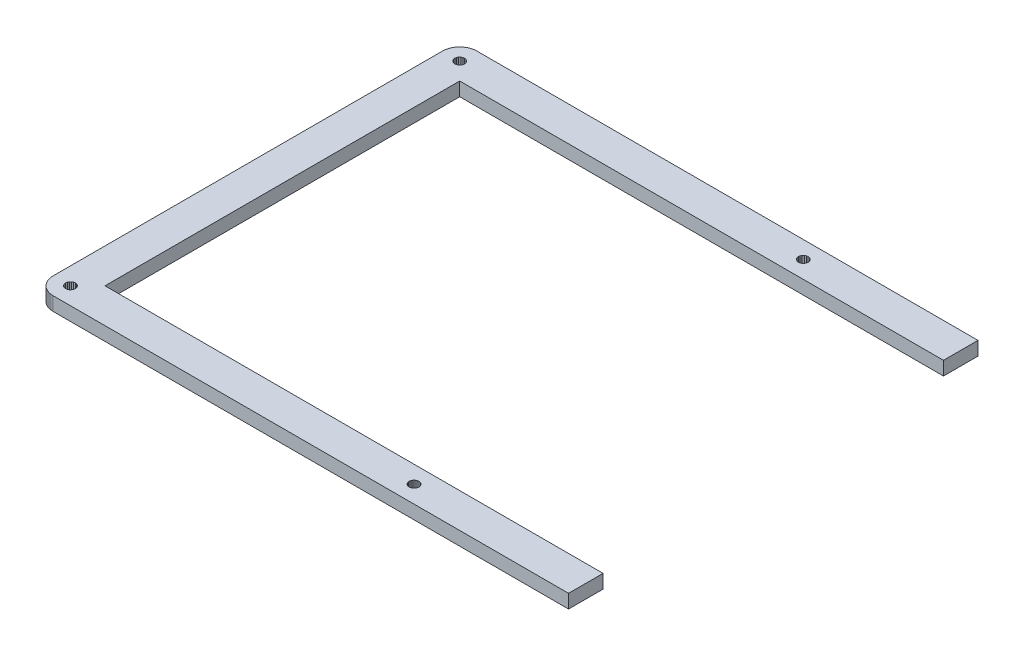
SolidWorks part; units mm, degrees
material "Copper"
ref_plane "Front Plane" through (0, 0, 0) normal (0, 0, 1) x (1, 0, 0)
ref_plane "Top Plane" through (0, 0, 0) normal (0, 1, 0) x (1, 0, 0)
ref_plane "Right Plane" through (0, 0, 0) normal (1, 0, 0) x (0, 0, -1)
sketch "Sketch1" plane through (0, 0, 0) normal (0, 1, 0) x (1, 0, 0)
  line L0 (365.806, 147.967) -> (366.279, 147.949)
  line L1 (366.279, 147.949) -> (366.748, 147.894)
  line L2 (366.748, 147.894) -> (367.21, 147.803)
  line L3 (367.21, 147.803) -> (367.661, 147.675)
  line L4 (367.661, 147.675) -> (368.106, 147.511)
  line L5 (368.106, 147.511) -> (368.533, 147.314)
  line L6 (368.533, 147.314) -> (368.942, 147.085)
  line L7 (368.942, 147.085) -> (369.334, 146.822)
  line L8 (369.334, 146.822) -> (369.704, 146.529)
  line L9 (369.704, 146.529) -> (370.05, 146.21)
  line L10 (370.05, 146.21) -> (370.371, 145.865)
  line L11 (370.371, 145.865) -> (370.664, 145.495)
  line L12 (370.664, 145.495) -> (370.925, 145.102)
  line L13 (370.925, 145.102) -> (371.154, 144.691)
  line L14 (371.154, 144.691) -> (371.352, 144.264)
  line L15 (371.352, 144.264) -> (371.514, 143.822)
  line L16 (371.514, 143.822) -> (371.641, 143.368)
  line L17 (371.641, 143.368) -> (371.733, 142.907)
  line L18 (371.733, 142.907) -> (371.789, 142.44)
  line L19 (371.789, 142.44) -> (371.807, 141.967)
  line L20 (371.807, 141.967) -> (371.807, 6.0909)
  line L21 (371.807, 6.0909) -> (371.789, 5.621)
  line L22 (371.789, 5.621) -> (371.733, 5.1539)
  line L23 (371.733, 5.1539) -> (371.641, 4.6909)
  line L24 (371.641, 4.6909) -> (371.514, 4.2375)
  line L25 (371.514, 4.2375) -> (371.352, 3.7951)
  line L26 (371.352, 3.7951) -> (371.154, 3.3679)
  line L27 (371.154, 3.3679) -> (370.925, 2.9573)
  line L28 (370.925, 2.9573) -> (370.664, 2.5645)
  line L29 (370.664, 2.5645) -> (370.371, 2.1966)
  line L30 (370.371, 2.1966) -> (370.05, 1.8493)
  line L31 (370.05, 1.8493) -> (369.704, 1.5296)
  line L32 (369.704, 1.5296) -> (369.334, 1.2375)
  line L33 (369.334, 1.2375) -> (368.942, 0.9757)
  line L34 (368.942, 0.9757) -> (368.533, 0.7455)
  line L35 (368.533, 0.7455) -> (368.106, 0.5498)
  line L36 (368.106, 0.5498) -> (367.661, 0.3859)
  line L37 (367.661, 0.3859) -> (367.21, 0.2577)
  line L38 (367.21, 0.2577) -> (366.748, 0.1654)
  line L39 (366.748, 0.1654) -> (366.279, 0.1102)
  line L40 (366.279, 0.1102) -> (365.806, 0.091)
  line L41 (365.806, 0.091) -> (6.095, 0.091)
  line L42 (6.095, 0.091) -> (5.6238, 0.1102)
  line L43 (5.6238, 0.1102) -> (5.1553, 0.1654)
  line L44 (5.1553, 0.1654) -> (4.6936, 0.2577)
  line L45 (4.6936, 0.2577) -> (4.2402, 0.3859)
  line L46 (4.2402, 0.3859) -> (3.7979, 0.5498)
  line L47 (3.7979, 0.5498) -> (3.3707, 0.7455)
  line L48 (3.3707, 0.7455) -> (2.96, 0.9757)
  line L49 (2.96, 0.9757) -> (2.5673, 1.2375)
  line L50 (2.5673, 1.2375) -> (2.198, 1.5296)
  line L51 (2.198, 1.5296) -> (1.8521, 1.8493)
  line L52 (1.8521, 1.8493) -> (1.5324, 2.1966)
  line L53 (1.5324, 2.1966) -> (1.2402, 2.5645)
  line L54 (1.2402, 2.5645) -> (0.9784, 2.9573)
  line L55 (0.9784, 2.9573) -> (0.7483, 3.3679)
  line L56 (0.7483, 3.3679) -> (0.5512, 3.7951)
  line L57 (0.5512, 3.7951) -> (0.3872, 4.2375)
  line L58 (0.3872, 4.2375) -> (0.2591, 4.6909)
  line L59 (0.2591, 4.6909) -> (0.1681, 5.1539)
  line L60 (0.1681, 5.1539) -> (0.113, 5.621)
  line L61 (0.113, 5.621) -> (0.0937, 6.0923)
  line L62 (0.0937, 6.0923) -> (0.0951, 141.967)
  line L63 (0.0951, 141.967) -> (0.113, 142.44)
  line L64 (0.113, 142.44) -> (0.1681, 142.907)
  line L65 (0.1681, 142.907) -> (0.2591, 143.368)
  line L66 (0.2591, 143.368) -> (0.3872, 143.822)
  line L67 (0.3872, 143.822) -> (0.5512, 144.264)
  line L68 (0.5512, 144.264) -> (0.7483, 144.691)
  line L69 (0.7483, 144.691) -> (0.9784, 145.102)
  line L70 (0.9784, 145.102) -> (1.2402, 145.495)
  line L71 (1.2402, 145.495) -> (1.5324, 145.865)
  line L72 (1.5324, 145.865) -> (1.8521, 146.21)
  line L73 (1.8521, 146.21) -> (2.198, 146.529)
  line L74 (2.198, 146.529) -> (2.5673, 146.822)
  line L75 (2.5673, 146.822) -> (2.96, 147.085)
  line L76 (2.96, 147.085) -> (3.3707, 147.314)
  line L77 (3.3707, 147.314) -> (3.7979, 147.511)
  line L78 (3.7979, 147.511) -> (4.2402, 147.675)
  line L79 (4.2402, 147.675) -> (4.6936, 147.803)
  line L80 (4.6936, 147.803) -> (5.1553, 147.894)
  line L81 (5.1553, 147.894) -> (5.6238, 147.949)
  line L82 (5.6238, 147.949) -> (6.095, 147.968)
  line L83 (6.095, 147.968) -> (365.806, 147.967)
  line L84 (365.252, 7.757) -> (364.769, 7.5117)
  line L85 (364.769, 7.5117) -> (364.388, 7.13)
  line L86 (364.388, 7.13) -> (364.141, 6.6504)
  line L87 (364.141, 6.6504) -> (364.06, 6.1157)
  line L88 (364.06, 6.1157) -> (364.141, 5.5838)
  line L89 (364.141, 5.5838) -> (364.388, 5.1029)
  line L90 (364.388, 5.1029) -> (364.769, 4.7211)
  line L91 (364.769, 4.7211) -> (365.252, 4.4759)
  line L92 (365.252, 4.4759) -> (365.781, 4.3918)
  line L93 (365.781, 4.3918) -> (366.317, 4.4759)
  line L94 (366.317, 4.4759) -> (366.797, 4.7211)
  line L95 (366.797, 4.7211) -> (367.178, 5.1029)
  line L96 (367.178, 5.1029) -> (367.425, 5.5838)
  line L97 (367.425, 5.5838) -> (367.506, 6.1157)
  line L98 (367.506, 6.1157) -> (367.425, 6.6504)
  line L99 (367.425, 6.6504) -> (367.178, 7.13)
  line L100 (367.178, 7.13) -> (366.797, 7.5117)
  line L101 (366.797, 7.5117) -> (366.317, 7.757)
  line L102 (366.317, 7.757) -> (365.781, 7.8411)
  line L103 (365.781, 7.8411) -> (365.252, 7.757)
  line L104 (245.361, 7.757) -> (244.88, 7.5117)
  line L105 (244.88, 7.5117) -> (244.5, 7.13)
  line L106 (244.5, 7.13) -> (244.255, 6.6504)
  line L107 (244.255, 6.6504) -> (244.169, 6.1157)
  line L108 (244.169, 6.1157) -> (244.255, 5.5838)
  line L109 (244.255, 5.5838) -> (244.5, 5.1029)
  line L110 (244.5, 5.1029) -> (244.88, 4.7211)
  line L111 (244.88, 4.7211) -> (245.361, 4.4759)
  line L112 (245.361, 4.4759) -> (245.894, 4.3918)
  line L113 (245.894, 4.3918) -> (246.428, 4.4759)
  line L114 (246.428, 4.4759) -> (246.908, 4.7211)
  line L115 (246.908, 4.7211) -> (247.29, 5.1029)
  line L116 (247.29, 5.1029) -> (247.536, 5.5838)
  line L117 (247.536, 5.5838) -> (247.62, 6.1157)
  line L118 (247.62, 6.1157) -> (247.536, 6.6504)
  line L119 (247.536, 6.6504) -> (247.29, 7.13)
  line L120 (247.29, 7.13) -> (246.908, 7.5117)
  line L121 (246.908, 7.5117) -> (246.428, 7.757)
  line L122 (246.428, 7.757) -> (245.894, 7.8411)
  line L123 (245.894, 7.8411) -> (245.361, 7.757)
  line L124 (125.473, 7.757) -> (124.992, 7.5117)
  line L125 (124.992, 7.5117) -> (124.612, 7.13)
  line L126 (124.612, 7.13) -> (124.365, 6.6504)
  line L127 (124.365, 6.6504) -> (124.281, 6.1157)
  line L128 (124.281, 6.1157) -> (124.365, 5.5838)
  line L129 (124.365, 5.5838) -> (124.612, 5.1029)
  line L130 (124.612, 5.1029) -> (124.992, 4.7211)
  line L131 (124.992, 4.7211) -> (125.473, 4.4759)
  line L132 (125.473, 4.4759) -> (126.007, 4.3918)
  line L133 (126.007, 4.3918) -> (126.54, 4.4759)
  line L134 (126.54, 4.4759) -> (127.021, 4.7211)
  line L135 (127.021, 4.7211) -> (127.403, 5.1029)
  line L136 (127.403, 5.1029) -> (127.648, 5.5838)
  line L137 (127.648, 5.5838) -> (127.732, 6.1157)
  line L138 (127.732, 6.1157) -> (127.648, 6.6504)
  line L139 (127.648, 6.6504) -> (127.403, 7.13)
  line L140 (127.403, 7.13) -> (127.021, 7.5117)
  line L141 (127.021, 7.5117) -> (126.54, 7.757)
  line L142 (126.54, 7.757) -> (126.007, 7.8411)
  line L143 (126.007, 7.8411) -> (125.473, 7.757)
  line L144 (5.5852, 7.757) -> (5.1056, 7.5117)
  line L145 (5.1056, 7.5117) -> (4.7239, 7.13)
  line L146 (4.7239, 7.13) -> (4.4786, 6.6504)
  line L147 (4.4786, 6.6504) -> (4.3932, 6.1157)
  line L148 (4.3932, 6.1157) -> (4.4786, 5.5838)
  line L149 (4.4786, 5.5838) -> (4.7239, 5.1029)
  line L150 (4.7239, 5.1029) -> (5.1056, 4.7211)
  line L151 (5.1056, 4.7211) -> (5.5852, 4.4759)
  line L152 (5.5852, 4.4759) -> (6.1185, 4.3918)
  line L153 (6.1185, 4.3918) -> (6.6532, 4.4759)
  line L154 (6.6532, 4.4759) -> (7.1327, 4.7211)
  line L155 (7.1327, 4.7211) -> (7.5145, 5.1029)
  line L156 (7.5145, 5.1029) -> (7.7597, 5.5838)
  line L157 (7.7597, 5.5838) -> (7.8438, 6.1157)
  line L158 (7.8438, 6.1157) -> (7.7597, 6.6504)
  line L159 (7.7597, 6.6504) -> (7.5145, 7.13)
  line L160 (7.5145, 7.13) -> (7.1327, 7.5117)
  line L161 (7.1327, 7.5117) -> (6.6532, 7.757)
  line L162 (6.6532, 7.757) -> (6.1185, 7.8411)
  line L163 (6.1185, 7.8411) -> (5.5852, 7.757)
  line L164 (12.1447, 135.919) -> (359.759, 135.919)
  line L165 (359.759, 135.919) -> (359.759, 12.1405)
  line L166 (359.759, 12.1405) -> (12.1447, 12.1405)
  line L167 (12.1447, 12.1405) -> (12.1447, 135.919)
  line L168 (125.473, 143.583) -> (124.992, 143.338)
  line L169 (124.992, 143.338) -> (124.612, 142.956)
  line L170 (124.612, 142.956) -> (124.365, 142.477)
  line L171 (124.365, 142.477) -> (124.281, 141.942)
  line L172 (124.281, 141.942) -> (124.365, 141.409)
  line L173 (124.365, 141.409) -> (124.612, 140.929)
  line L174 (124.612, 140.929) -> (124.992, 140.547)
  line L175 (124.992, 140.547) -> (125.473, 140.302)
  line L176 (125.473, 140.302) -> (126.007, 140.217)
  line L177 (126.007, 140.217) -> (126.54, 140.302)
  line L178 (126.54, 140.302) -> (127.021, 140.547)
  line L179 (127.021, 140.547) -> (127.403, 140.929)
  line L180 (127.403, 140.929) -> (127.648, 141.409)
  line L181 (127.648, 141.409) -> (127.732, 141.942)
  line L182 (127.732, 141.942) -> (127.648, 142.477)
  line L183 (127.648, 142.477) -> (127.403, 142.956)
  line L184 (127.403, 142.956) -> (127.021, 143.338)
  line L185 (127.021, 143.338) -> (126.54, 143.583)
  line L186 (126.54, 143.583) -> (126.007, 143.667)
  line L187 (126.007, 143.667) -> (125.473, 143.583)
  line L188 (245.361, 143.583) -> (244.88, 143.338)
  line L189 (244.88, 143.338) -> (244.5, 142.956)
  line L190 (244.5, 142.956) -> (244.255, 142.477)
  line L191 (244.255, 142.477) -> (244.169, 141.942)
  line L192 (244.169, 141.942) -> (244.255, 141.409)
  line L193 (244.255, 141.409) -> (244.5, 140.929)
  line L194 (244.5, 140.929) -> (244.88, 140.547)
  line L195 (244.88, 140.547) -> (245.361, 140.302)
  line L196 (245.361, 140.302) -> (245.894, 140.217)
  line L197 (245.894, 140.217) -> (246.428, 140.302)
  line L198 (246.428, 140.302) -> (246.908, 140.547)
  line L199 (246.908, 140.547) -> (247.29, 140.929)
  line L200 (247.29, 140.929) -> (247.536, 141.409)
  line L201 (247.536, 141.409) -> (247.62, 141.942)
  line L202 (247.62, 141.942) -> (247.536, 142.477)
  line L203 (247.536, 142.477) -> (247.29, 142.956)
  line L204 (247.29, 142.956) -> (246.908, 143.338)
  line L205 (246.908, 143.338) -> (246.428, 143.583)
  line L206 (246.428, 143.583) -> (245.894, 143.667)
  line L207 (245.894, 143.667) -> (245.361, 143.583)
  line L208 (365.252, 143.583) -> (364.769, 143.338)
  line L209 (364.769, 143.338) -> (364.388, 142.956)
  line L210 (364.388, 142.956) -> (364.141, 142.477)
  line L211 (364.141, 142.477) -> (364.06, 141.942)
  line L212 (364.06, 141.942) -> (364.141, 141.409)
  line L213 (364.141, 141.409) -> (364.388, 140.929)
  line L214 (364.388, 140.929) -> (364.769, 140.547)
  line L215 (364.769, 140.547) -> (365.252, 140.302)
  line L216 (365.252, 140.302) -> (365.781, 140.217)
  line L217 (365.781, 140.217) -> (366.317, 140.302)
  line L218 (366.317, 140.302) -> (366.797, 140.547)
  line L219 (366.797, 140.547) -> (367.178, 140.929)
  line L220 (367.178, 140.929) -> (367.425, 141.409)
  line L221 (367.425, 141.409) -> (367.506, 141.942)
  line L222 (367.506, 141.942) -> (367.425, 142.477)
  line L223 (367.425, 142.477) -> (367.178, 142.956)
  line L224 (367.178, 142.956) -> (366.797, 143.338)
  line L225 (366.797, 143.338) -> (366.317, 143.583)
  line L226 (366.317, 143.583) -> (365.781, 143.667)
  line L227 (365.781, 143.667) -> (365.252, 143.583)
  line L228 (5.5852, 143.583) -> (5.1056, 143.338)
  line L229 (5.1056, 143.338) -> (4.7239, 142.956)
  line L230 (4.7239, 142.956) -> (4.4786, 142.477)
  line L231 (4.4786, 142.477) -> (4.3932, 141.942)
  line L232 (4.3932, 141.942) -> (4.4786, 141.409)
  line L233 (4.4786, 141.409) -> (4.7239, 140.929)
  line L234 (4.7239, 140.929) -> (5.1056, 140.547)
  line L235 (5.1056, 140.547) -> (5.5852, 140.302)
  line L236 (5.5852, 140.302) -> (6.1185, 140.217)
  line L237 (6.1185, 140.217) -> (6.6532, 140.302)
  line L238 (6.6532, 140.302) -> (7.1327, 140.547)
  line L239 (7.1327, 140.547) -> (7.5145, 140.929)
  line L240 (7.5145, 140.929) -> (7.7597, 141.409)
  line L241 (7.7597, 141.409) -> (7.8438, 141.942)
  line L242 (7.8438, 141.942) -> (7.7597, 142.477)
  line L243 (7.7597, 142.477) -> (7.5145, 142.956)
  line L244 (7.5145, 142.956) -> (7.1327, 143.338)
  line L245 (7.1327, 143.338) -> (6.6532, 143.583)
  line L246 (6.6532, 143.583) -> (6.1185, 143.667)
  line L247 (6.1185, 143.667) -> (5.5852, 143.583)
  line L248 (185.9505, 147.9675) -> (185.9505, 0.091)
extrude "Boss-Extrude2" add sketch "Sketch1" along normal blind 4.7625 contours L248 L83 L82 L81 L80 L79 L78 L77 L76 L75 L74 L73 L72 L71 L70 L69 L68 L67 L66 L65 L64 L63 L62 L61 L60 L59 L58 L57 L56 L55 L54 L53 L52 L51 L50 L49 L48 L47 L46 L45 L44 L43 L42 L41 L166 L167 L164 L247 L246 region at (183.5754, 0, -141.9433)
sketch "Sketch2" plane through (0, 4.7625, 0) normal (0, 1, 0) x (1, 0, 0)
  line L1 (185.9505, 147.9675) -> (185.9505, 135.919) construction
  line L2 (12.1447, 135.919) -> (185.9505, 135.919) construction
  line L4 (180.9505, 141.9433) -> (180.9505, 147.9675)
  line L5 (180.9505, 147.9675) -> (185.9505, 147.9675)
  line L6 (185.9505, 141.9433) -> (185.9505, 147.9675)
  line L8 (185.9505, 141.9433) -> (185.9505, 135.919)
  line L9 (185.9505, 135.919) -> (180.9505, 135.919)
  line L10 (180.9505, 141.9433) -> (180.9505, 135.919)
extrude "Cut-Extrude2" cut sketch "Sketch2" against normal blind 4.7625
sketch "Sketch3" plane through (0, 0, -147.9675) normal (0, 0, 1) x (1, 0, 0)
  line L1 (180.9505, 0) -> (185.9505, 0)
  line L2 (180.9505, 0) -> (180.9505, 4.7625)
  line L3 (180.9505, 4.7625) -> (185.9505, 4.7625)
  line L4 (185.9505, 0) -> (185.9505, 4.7625)
extrude "Cut-Extrude3" cut sketch "Sketch3" against normal blind 4.7625
